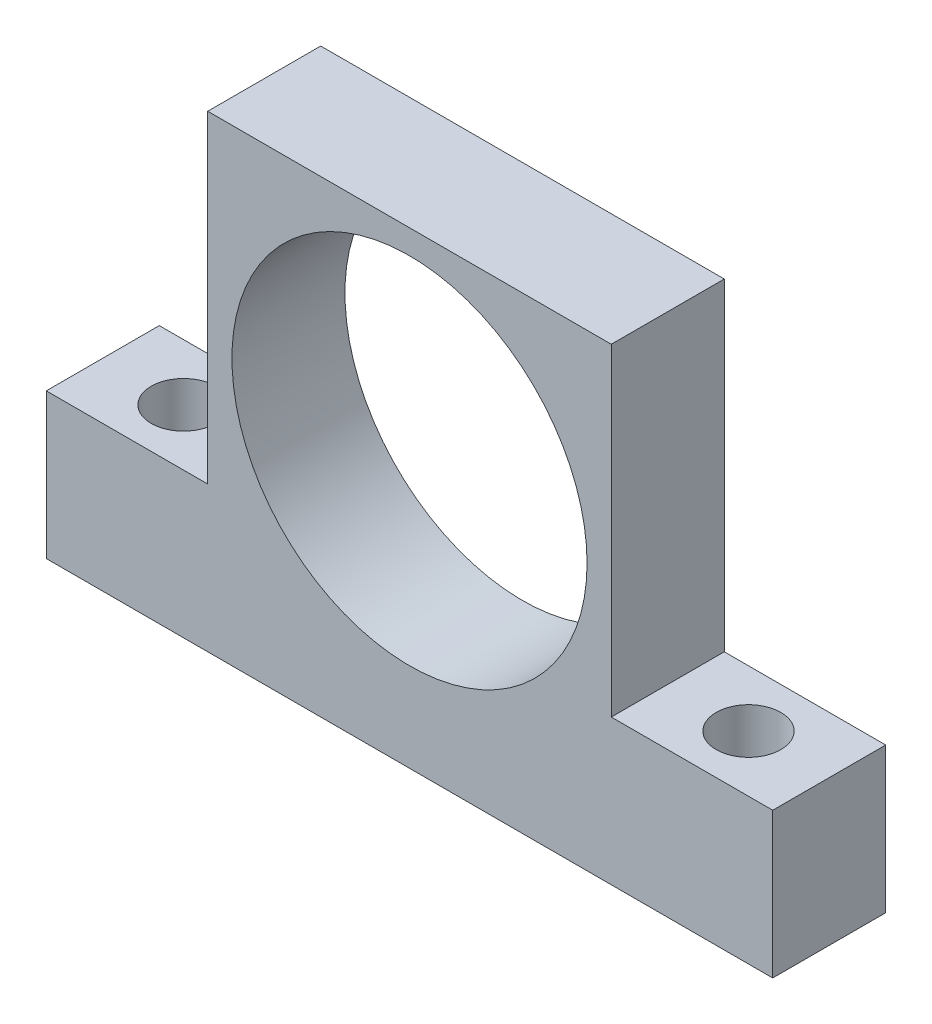
SolidWorks part; units mm, degrees
material "ABS"
ref_plane "Front Plane" through (0, 0, 0) normal (0, 0, 1) x (1, 0, 0)
ref_plane "Top Plane" through (0, 0, 0) normal (0, 1, 0) x (1, 0, 0)
ref_plane "Right Plane" through (0, 0, 0) normal (1, 0, 0) x (0, 0, -1)
sketch "Sketch1" plane through (0, 0, 0) normal (0, 0, 1) x (1, 0, 0)
  line L1 (-12.5, 12.5) -> (12.5, 12.5)
  line L2 (-12.5, 12.5) -> (-12.5, -16.5)
  line L3 (-12.5, -16.5) -> (12.5, -16.5)
  line L4 (12.5, 12.5) -> (12.5, -16.5)
  line L5 (-12.5, 12.5) -> (12.5, -16.5) construction
  line L6 (-12.5, -16.5) -> (12.5, 12.5) construction
  line L7 (12.5, -16.5) -> (22.5, -16.5)
  line L8 (12.5, -16.5) -> (12.5, -7.5)
  line L9 (12.5, -7.5) -> (22.5, -7.5)
  line L10 (22.5, -16.5) -> (22.5, -7.5)
  line L11 (12.5, -16.5) -> (22.5, -7.5) construction
  line L12 (12.5, -7.5) -> (22.5, -16.5) construction
  line L13 (-12.5, -16.5) -> (-22.5, -16.5)
  line L14 (-12.5, -16.5) -> (-12.5, -7.5)
  line L15 (-12.5, -7.5) -> (-22.5, -7.5)
  line L16 (-22.5, -16.5) -> (-22.5, -7.5)
  line L17 (-12.5, -16.5) -> (-22.5, -7.5) construction
  line L18 (-12.5, -7.5) -> (-22.5, -16.5) construction
  circle A0 centre (0, 0) radius 4.1
  circle A1 centre (0, 0) radius 11
  point P8 (0, 0)
  point P14 (17.5, -12)
  point P16 (-17.5, -12)
  point P17 (0, 0)
  dimension "D4" = 8.2
  dimension "D5" = 22
  dimension "D1" = 12.5
  dimension "D2" = 29
  dimension "D3" = 25
  dimension "D6" = 10
  dimension "D7" = 9
  dimension "D8" = 10
  dimension "D9" = 9
  dimension "D10" = 12.5
extrude "Boss-Extrude1" add sketch "Sketch1" along normal blind 7 contours L4 L1 L2 L3 A1 | L16 L13 L2 L15 | L7 L10 L9 L4 region at (0, 12.1171, 0) region at (-17.5, -12, 0) region at (17.5, -12, 0)
sketch "Sketch2" plane through (0, -7.5, 0) normal (0, 1, 0) x (1, 0, 0)
  line L0 (-22.5, 0) -> (-12.5, -7)
  line L1 (-12.5, -7) -> (-22.5, -7)
  line L2 (-22.5, -7) -> (-12.5, 0)
  line L3 (12.5, 0) -> (22.5, -7)
  line L4 (22.5, -7) -> (22.5, 0)
  line L5 (22.5, 0) -> (12.5, -7)
  circle A0 centre (-17.5, -3.5) radius 2
  circle A1 centre (17.5, -3.5) radius 2
  dimension "D1" = 4
  dimension "D2" = 4
extrude "Cut-Extrude1" cut sketch "Sketch2" against normal blind 7 contours L0 A0 L2 | L2 A0 L0 | L0 A0 L2 | L2 A0 L0 | A1 region at (-17.5, -7.5, 2.3623) region at (-18.752, -7.5, 3.5) region at (-16.248, -7.5, 3.5) region at (-17.5, -7.5, 4.6377)
